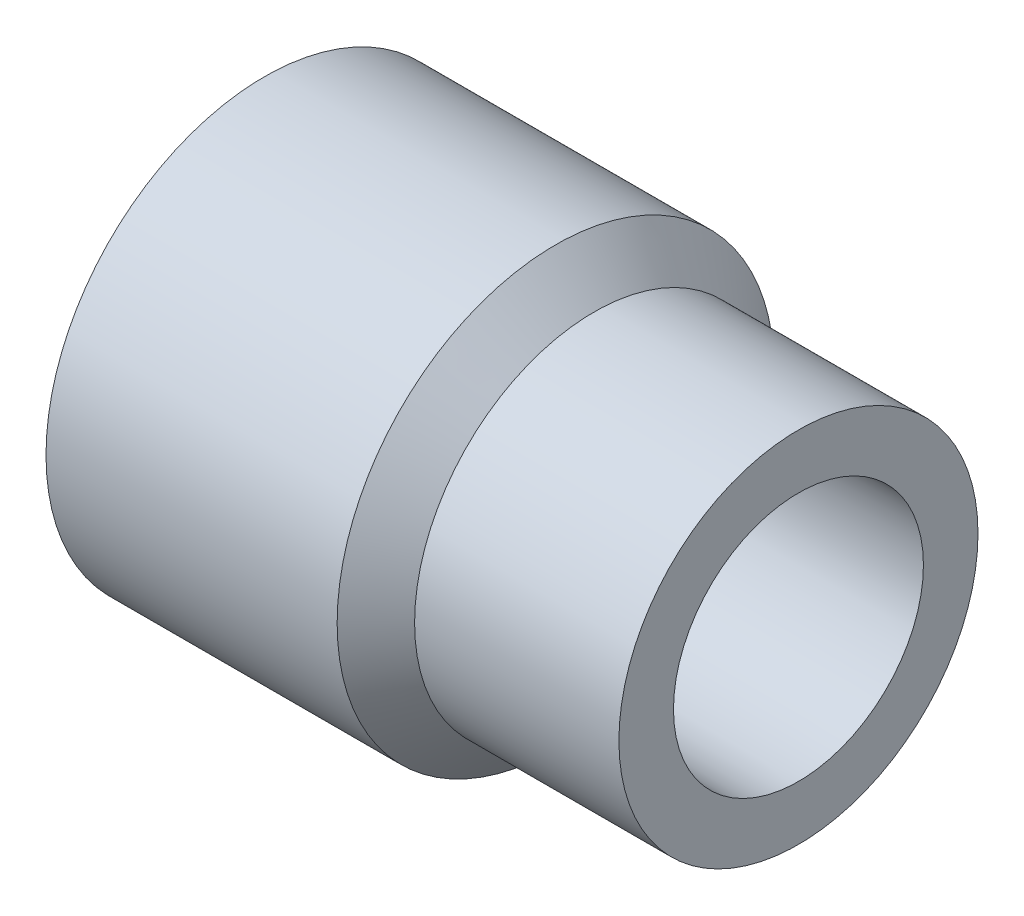
SolidWorks part; units mm, degrees
ref_plane "Front Plane" through (0, 0, 0) normal (0, 0, 1) x (1, 0, 0)
ref_plane "Top Plane" through (0, 0, 0) normal (0, 1, 0) x (1, 0, 0)
ref_plane "Right Plane" through (0, 0, 0) normal (1, 0, 0) x (0, 0, -1)
sketch "Sketch0" plane through (0, 0, 0) normal (0, 0, 1) x (1, 0, 0)
  line L0 (-28.702, 0) -> (3.048, 0) construction
  line L2 (0, 0) -> (3.048, 0) construction
  line L3 (-28.702, 0) -> (28.702, 0) construction
  line L4 (-28.702, 23.495) -> (-28.702, -23.495) construction
  line L5 (0, 16.637) -> (-28.702, 16.8275) construction
  line L6 (0, 16.637) -> (0, -16.637) construction
  line L7 (0, -16.637) -> (-28.702, -16.8275) construction
  line L8 (-28.702, 16.8275) -> (-28.702, -16.8275) construction
  line L9 (28.702, 13.4366) -> (28.702, -13.4366) construction
  line L10 (28.702, 19.304) -> (28.702, -19.304) construction
  line L11 (3.048, 9.4234) -> (3.048, -9.4234) construction
  line L12 (3.048, 13.2842) -> (3.048, -13.2842) construction
  line L13 (3.048, -13.2842) -> (28.702, -13.4366) construction
  line L14 (0, 12.1539) -> (0, -12.1539) construction
  line L15 (3.048, 13.2842) -> (28.702, 13.4366) construction
  dimension "N" = 3.048
  dimension "M" = 46.99
  dimension "OD A" = 33.655
  dimension "OD B" = 33.274
  dimension "ID" = 24.3078
  dimension "L" = 57.404
  dimension "ID2" = 18.8468
  dimension "OD B2" = 26.5684
  dimension "OD A2" = 26.8732
  dimension "M2" = 38.608
  dimension "C" = 28.702
  dimension "C2" = 25.654
sketch "Sketch1" plane through (0, 0, 0) normal (0, 0, 1) x (1, 0, 0)
  line L0 (-28.702, 0) -> (3.048, 0) construction
  line L1 (-28.702, 0) -> (3.048, 0) construction
  line L2 (0, -16.637) -> (5.2135, -11.3538) construction
  line L3 (0, -26.1295) -> (-4.7458, -21.4462) construction
  line L4 (-28.702, -23.495) -> (-28.702, -16.8275)
  line L5 (-28.702, -16.8275) -> (0, -16.637)
  line L6 (3.048, -11.3538) -> (1.0918, -11.3538) construction
  line L7 (1.0918, -11.3538) -> (3.048, -13.2842) construction
  line L8 (2.5997, -23.495) -> (6.7355, -19.304)
  line L9 (2.5997, -23.495) -> (-28.702, -23.495)
  line L10 (0, 0) -> (0, -26.1295) construction
  line L11 (1.0918, -11.3538) -> (5.2135, -11.3538) construction
  line L12 (3.048, -13.2842) -> (28.702, -13.4366)
  line L13 (28.702, -13.4366) -> (28.702, -19.304)
  line L14 (28.702, -19.304) -> (6.7355, -19.304)
  line L15 (3.048, -9.4234) -> (3.048, -13.2842) construction
  line L16 (0, -16.637) -> (2.0699, -11.3538)
  line L17 (2.0699, -11.3538) -> (2.559, -11.3538)
  line L18 (2.559, -11.3538) -> (3.048, -13.2842)
  line L19 (2.559, -11.3538) -> (3.048, -11.3538) construction
  dimension "D1" = 45
revolve "Revolve1" add sketch "Sketch1" angle 360 about L1
